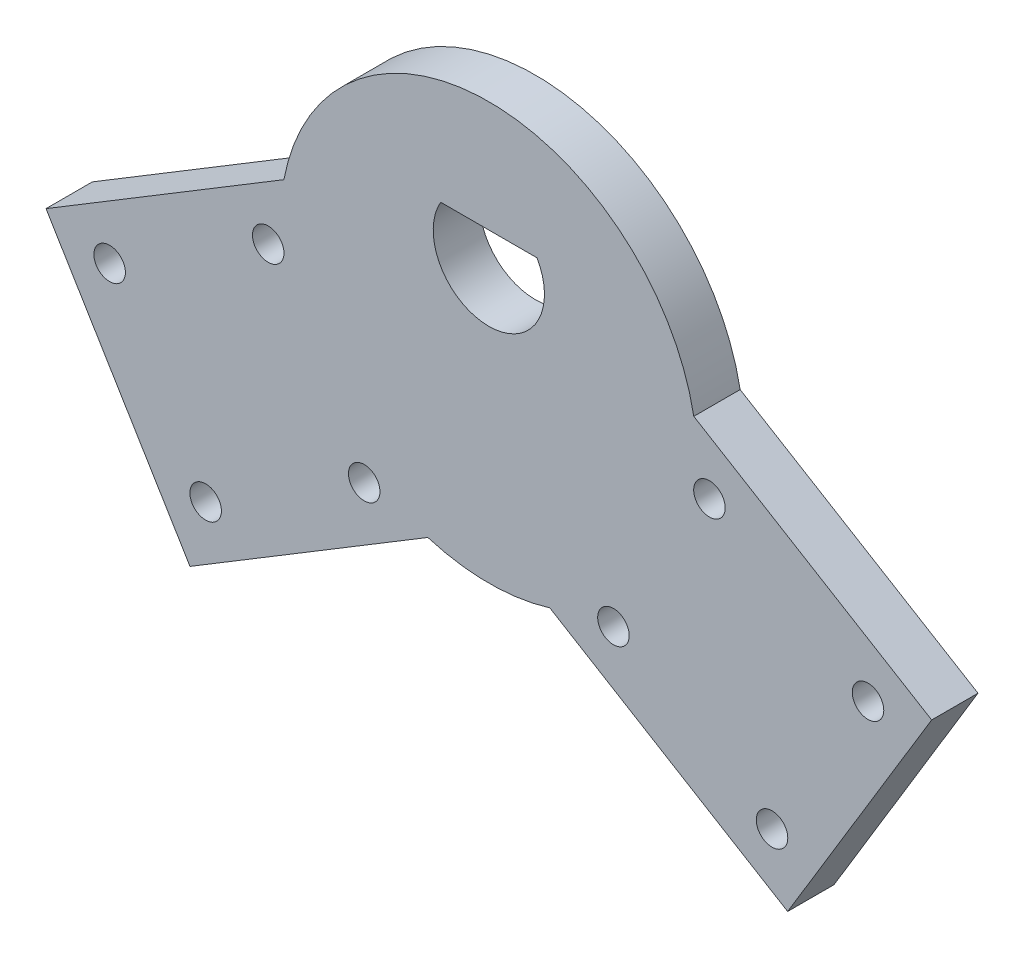
SolidWorks part; units mm, degrees
material "PLA 15%"
ref_plane "Front Plane" through (0, 0, 0) normal (0, 0, 1) x (1, 0, 0)
ref_plane "Top Plane" through (0, 0, 0) normal (0, 1, 0) x (1, 0, 0)
ref_plane "Right Plane" through (0, 0, 0) normal (1, 0, 0) x (0, 0, -1)
sketch "Sketch2" plane through (0, 0, 0) normal (0, 0, 1) x (1, 0, 0)
  line L8 (0, 0) -> (0, -22.5) construction
  line L9 (0, 0) -> (6.5784, -21.5169) construction
  line L10 (0, 0) -> (-6.5784, -21.5169) construction
  line L11 (6.5784, -21.5169) -> (22.1146, 4.1469) construction
  line L12 (6.5784, -21.5169) -> (32.2421, -37.053)
  line L13 (22.1146, 4.1469) -> (47.7783, -11.3893)
  line L14 (32.2421, -37.053) -> (47.7783, -11.3893)
  line L15 (-6.5784, -21.5169) -> (-22.1146, 4.1469) construction
  line L16 (-6.5784, -21.5169) -> (-32.2421, -37.053)
  line L17 (-22.1146, 4.1469) -> (-47.7783, -11.3893)
  line L18 (-32.2421, -37.053) -> (-47.7783, -11.3893)
  line L19 (-15.6807, -16.1358) -> (-21.5667, -6.4129) construction
  line L20 (-23.8025, -2.7198) -> (-40.9116, -13.0772) construction
  line L21 (-30.5542, -30.1864) -> (-40.9116, -13.0772) construction
  line L22 (-13.445, -19.8289) -> (-30.5542, -30.1864) construction
  line L23 (13.445, -19.8289) -> (15.6807, -16.1358) construction
  line L24 (23.8025, -2.7198) -> (40.9116, -13.0772) construction
  line L25 (30.5542, -30.1864) -> (40.9116, -13.0772) construction
  line L26 (13.445, -19.8289) -> (30.5542, -30.1864) construction
  line L27 (-21.5667, -6.4129) -> (-23.8025, -2.7198) construction
  line L28 (-13.445, -19.8289) -> (-23.8025, -2.7198) construction
  line L29 (-13.445, -19.8289) -> (-15.6807, -16.1358) construction
  line L30 (15.6807, -16.1358) -> (21.5667, -6.4129) construction
  line L31 (21.5667, -6.4129) -> (23.8025, -2.7198) construction
  line L32 (13.445, -19.8289) -> (23.8025, -2.7198) construction
  line L33 (0, 22.5) -> (0, -22.5) construction
  line L34 (5.1962, 10.5) -> (-5.1962, 10.5)
  arc A0 (-21.5667, -6.4129) -> (-15.6807, -16.1358) centre (0, 0) ccw construction
  arc A1 (-22.1146, 4.1469) -> (-21.5667, -6.4129) centre (0, 0) ccw construction
  arc A2 (-15.6807, -16.1358) -> (-6.5784, -21.5169) centre (0, 0) ccw construction
  arc A3 (-6.5784, -21.5169) -> (6.5784, -21.5169) centre (0, 0) ccw
  arc A4 (15.6807, -16.1358) -> (21.5667, -6.4129) centre (0, 0) ccw construction
  arc A5 (22.1146, 4.1469) -> (-22.1146, 4.1469) centre (0, 0) ccw
  arc A6 (21.5667, -6.4129) -> (22.1146, 4.1469) centre (0, 0) ccw construction
  arc A7 (6.5784, -21.5169) -> (15.6807, -16.1358) centre (0, 0) ccw construction
  arc A8 (-5.1962, 10.5) -> (5.1962, 10.5) centre (0, 7.5) ccw
  arc A9 (-5.1962, 10.5) -> (5.1962, 10.5) centre (0, 7.5) cw construction
  point P23 (0, 9.9583)
  point P28 (0, 13.5)
  dimension "D5" = 45
  dimension "D10" = 6
  dimension "D1" = 17
  dimension "D2" = 17
  dimension "D3" = 30
  dimension "D4" = 30
  dimension "D6" = 30
  dimension "D7" = 30
  dimension "D9" = 30
  dimension "D11" = 3
  dimension "D8" = 5
extrude "Boss-Extrude1" add sketch "Sketch2" along normal blind 5 contours L13 A5 L17 L18 L16 A3 L12 L14 A8 L34
hole_wizard "M3 Clearance Hole1" positions "Sketch5" profile "Sketch6" hole size "M3" standard "ANSI Metric" end condition through all
sketch "Sketch5" plane through (0, 0, 5) normal (0, 0, 1) x (1, 0, 0)
  point P0 (-40.9116, -13.0772)
  point P3 (-23.8025, -2.7198)
  point P6 (-13.445, -19.8289)
  point P9 (-30.5542, -30.1864)
  point P12 (13.445, -19.8289)
  point P15 (23.8025, -2.7198)
  point P18 (40.9116, -13.0772)
  point P21 (30.5542, -30.1864)
sketch "Sketch6" plane through (-40.9116, -13.0772, 5) normal (1, 0, 0) x (0, -1, 0)
  line L0 (0, 0) -> (0, 5)
  line L1 (0, 5) -> (1.7, 5)
  line L2 (1.7, 5) -> (1.7, 0)
  line L5 (1.7, 0) -> (0, 0)
  line L11 (0, -6.35) -> (0, 107.95) construction
  dimension "Thru Hole Dia." = 3.4
  dimension "Thru Hole Depth" = 5
equation "\"dshaftdistance\"= 0.25"
